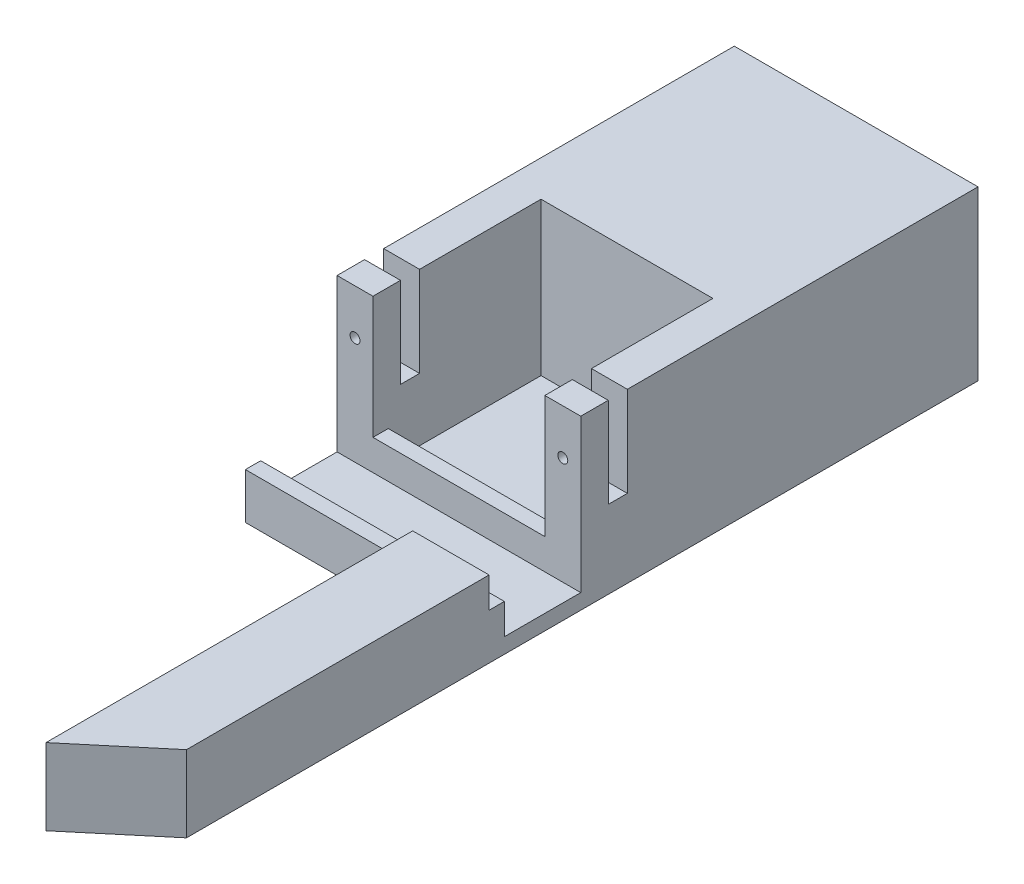
SolidWorks part; units mm, degrees
ref_plane "Front Plane" through (0, 0, 0) normal (0, 0, 1) x (1, 0, 0)
ref_plane "Top Plane" through (0, 0, 0) normal (0, 1, 0) x (1, 0, 0)
ref_plane "Right Plane" through (0, 0, 0) normal (1, 0, 0) x (0, 0, -1)
sketch "Sketch1" plane through (0, 0, 0) normal (0, 1, 0) x (1, 0, 0)
  line L1 (-15.95, 17) -> (15.95, 17)
  line L2 (-15.95, 17) -> (-15.95, -17)
  line L3 (-15.95, -17) -> (15.95, -17)
  line L4 (15.95, 17) -> (15.95, -17)
  line L5 (-15.95, 17) -> (15.95, -17) construction
  line L6 (-15.95, -17) -> (15.95, 17) construction
  point P0 (0, 0)
  dimension "D1" = 31.9
  dimension "D2" = 34
extrude "Boss-Extrude3" add sketch "Sketch1" along normal blind 2
sketch "Sketch2" plane through (0, 2, 0) normal (0, 1, 0) x (1, 0, 0)
  line L0 (0, 17) -> (0, -17) construction
  line L1 (-15.95, 17) -> (15.95, 17)
  line L2 (-15.95, 17) -> (-15.95, -17)
  line L3 (-15.95, -17) -> (15.95, -17)
  line L4 (15.95, 17) -> (15.95, -17)
  line L5 (-15.95, 17) -> (-11.25, 17)
  line L6 (-15.95, 17) -> (-15.95, -5)
  line L7 (-15.95, -5) -> (-11.25, -5)
  line L8 (-11.25, 17) -> (-11.25, -5)
  line L9 (15.95, -5) -> (11.25, -5)
  line L10 (11.25, 17) -> (11.25, -5)
  line L11 (15.95, 17) -> (11.25, 17)
  line L12 (15.95, 17) -> (15.95, -5)
  dimension "D1" = 4.7
  dimension "D2" = 22
  dimension "D3" = 22
  dimension "D5" = 4.7
extrude "Boss-Extrude4" add sketch "Sketch2" along normal blind 20 contours L6 L5 L8 L7 | L12 L9 L10 L11
sketch "Sketch3" plane through (0, 2, 0) normal (0, 1, 0) x (1, 0, 0)
  line L1 (-11.25, -5) -> (11.25, -5)
  line L2 (-11.25, -5) -> (-11.25, -3)
  line L3 (-11.25, -3) -> (11.25, -3)
  line L4 (11.25, -5) -> (11.25, -3)
  line L5 (-15.95, -17) -> (15.95, -17)
  line L6 (-15.95, -17) -> (-15.95, -15)
  line L7 (-15.95, -15) -> (15.95, -15)
  line L8 (15.95, -17) -> (15.95, -15)
  dimension "D1" = 22.5
  dimension "D2" = 2
  dimension "D3" = 2
  dimension "D4" = 31.9
extrude "Boss-Extrude5" add sketch "Sketch3" along normal blind 4
sketch "Sketch6" plane through (0, 22, 0) normal (0, 1, 0) x (1, 0, 0)
  line L0 (15.95, 17) -> (15.95, -5) construction
  line L1 (-15.95, 17) -> (15.95, 17)
  line L2 (-15.95, 17) -> (-15.95, -1.4)
  line L3 (-15.95, -1.4) -> (15.95, -1.4)
  line L4 (15.95, 17) -> (15.95, -1.4)
  line L6 (-15.95, -1.4) -> (15.95, -1.4)
  line L7 (-15.95, -1.4) -> (-15.95, 1.1)
  line L8 (-15.95, 1.1) -> (15.95, 1.1)
  line L9 (15.95, -1.4) -> (15.95, 1.1)
  line M10 (-11.25, -5) -> (-11.25, 17)
  dimension "D1" = 18.4
  dimension "D2" = 2.5
  dimension "D3" = 31.9
extrude "Cut-Extrude1" cut sketch "Sketch6" against normal blind 11.8 contours L8 L3 L4 M10 | L8 L2 L3 M10 region at (-13.6, 22, 0.15) region at (2.35, 22, 0.15)
sketch "Sketch7" plane through (0, 0, 5) normal (0, 0, 1) x (1, 0, 0)
  line L1 (-15.95, 22) -> (-11.25, 22) construction
  line L2 (-15.95, 22) -> (-15.95, 2) construction
  line L3 (15.95, 22) -> (11.25, 22) construction
  line L4 (11.25, 22) -> (11.25, 6) construction
  circle A0 centre (-13.6, 16.1) radius 0.65
  circle A1 centre (13.6, 16.1) radius 0.65
  point P22 (-13.6, 16.1)
  point P23 (13.6, 16.1)
  dimension "D3" = 1.3
  dimension "D4" = 1.3
  dimension "D1" = 5.9
  dimension "D2" = 2.35
  dimension "D5" = 5.9
  dimension "D6" = 2.35
extrude "Cut-Extrude2" cut sketch "Sketch7" against normal blind 4
sketch "Sketch8" plane through (0, 0, 0) normal (0, 1, 0) x (1, 0, 0)
  line L0 (5.95, -65) -> (15.95, -56.609)
  line L1 (15.95, -17) -> (5.95, -17)
  line L2 (15.95, -17) -> (15.95, -56.609)
  line L4 (5.95, -17) -> (5.95, -65)
  dimension "D1" = 60
extrude "Boss-Extrude6" add sketch "Sketch8" along normal blind 10 contours L2 L0 L4 L1
sketch "Sketch9" plane through (0, 0, -17) normal (0, 0, -1) x (-1, 0, 0)
  line L1 (15.95, 22) -> (-15.95, 22)
  line L2 (15.95, 22) -> (15.95, 0)
  line L3 (15.95, 0) -> (-15.95, 0)
  line L4 (-15.95, 22) -> (-15.95, 0)
extrude "Boss-Extrude7" add sketch "Sketch9" along normal blind 30
sketch "Sketch10" plane through (0, 0, -47) normal (0, 0, -1) x (-1, 0, 0)
  line L0 (0, 11) -> (0, 0) construction
  line L2 (0, 0) -> (-16.1072, 11) construction
  line L3 (-16.1072, 11) -> (15.95, 11) construction
  line L4 (15.95, 0) -> (15.95, 22) construction
  line L5 (0, 11) -> (0, 0) construction
  line L6 (4.235, 11) -> (4.235, 0)
  line L7 (-4.235, 11) -> (-4.235, 0)
  arc A0 (4.235, 11) -> (-4.235, 11) centre (0, 11) ccw
  arc A1 (-4.235, 0) -> (4.235, 0) centre (0, 0) ccw
  point P2 (0, 5.5)
extrude "Cut-Extrude3" cut sketch "Sketch10" against normal blind 6
sketch "Sketch11" plane through (0, 0, 0) normal (0, -1, 0) x (-1, 0, 0)
  line L0 (4.235, 47) -> (-4.235, 47) construction
  line L5 (-5, 34) -> (-8.5, 34)
  line L14 (5, 22) -> (-5, 22)
  line L15 (5, 22) -> (5, 34)
  line L29 (-5, 39) -> (-8.5, 39)
  line L30 (8.5, 39) -> (5, 39)
  line L31 (8.5, 39) -> (8.5, 34)
  line L32 (8.5, 34) -> (5, 34)
  line L33 (-8.5, 39) -> (-8.5, 34)
  line L34 (-5, 22) -> (-5, 34)
  line L37 (5, 39) -> (5, 41)
  line L38 (5, 41) -> (-5, 41)
  line L39 (-5, 39) -> (-5, 41)
  point P17 (0, 21.5)
  dimension "D1" = 2
  dimension "D2" = 10
  dimension "D3" = 3.5
  dimension "D4" = 6
  dimension "D5" = 5
  dimension "D6" = 12
  dimension "D7" = 17
extrude "Cut-Extrude7" cut sketch "Sketch11" against normal blind 15
